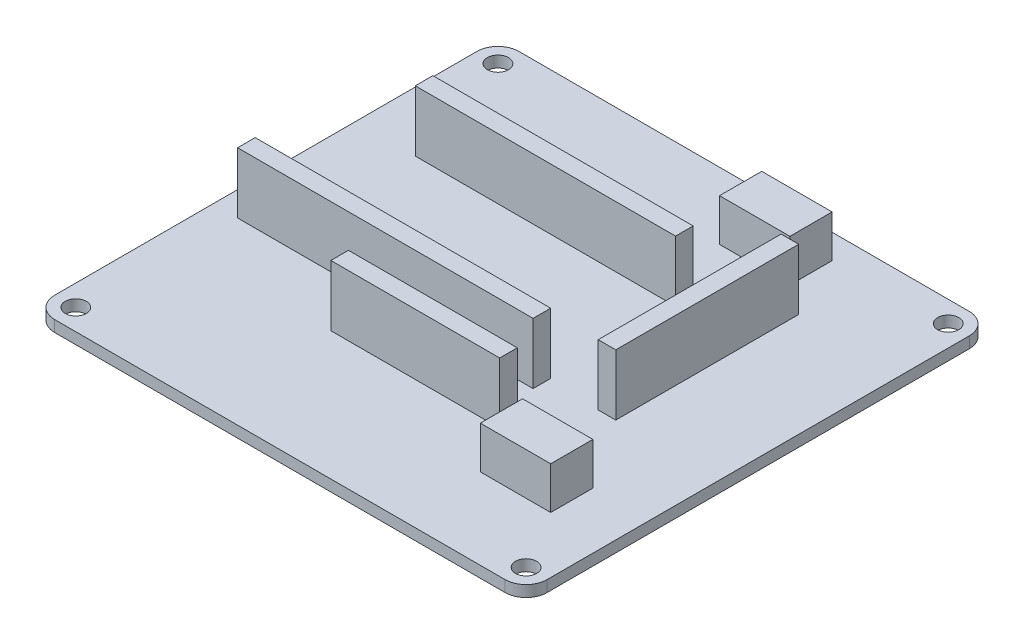
SolidWorks part; units mm, degrees
ref_plane "Front Plane" through (0, 0, 0) normal (0, 0, 1) x (1, 0, 0)
ref_plane "Top Plane" through (0, 0, 0) normal (0, 1, 0) x (1, 0, 0)
ref_plane "Right Plane" through (0, 0, 0) normal (1, 0, 0) x (0, 0, -1)
sketch "Sketch1" plane through (0, 0, 0) normal (0, 1, 0) x (1, 0, 0)
  line L0 (-32, 33) -> (32, 33)
  line L1 (35, -33) -> (-35, -33) construction
  line L2 (35, -33) -> (35, 33) construction
  line L3 (35, 33) -> (-35, 33) construction
  line L4 (-35, -33) -> (-35, 33) construction
  line L5 (35, -33) -> (-35, 33) construction
  line L6 (35, 33) -> (-35, -33) construction
  line L7 (-32, 30) -> (32, 30) construction
  line L8 (-32, 30) -> (-32, -30) construction
  line L9 (-32, -30) -> (32, -30) construction
  line L10 (32, 30) -> (32, -30) construction
  line L11 (35, 30) -> (35, -30)
  line L12 (32, -33) -> (-32, -33)
  line L13 (-35, -30) -> (-35, 30)
  circle A0 centre (-32, 30) radius 1.5
  circle A1 centre (32, 30) radius 1.5
  circle A2 centre (32, -30) radius 1.5
  circle A3 centre (-32, -30) radius 1.5
  arc A4 (-32, 33) -> (-35, 30) centre (-32, 30) ccw
  arc A5 (32, 33) -> (35, 30) centre (32, 30) cw
  arc A6 (35, -30) -> (32, -33) centre (32, -30) cw
  arc A7 (-35, -30) -> (-32, -33) centre (-32, -30) ccw
  point P0 (0, 0)
  point P8 (0, 0)
  point P14 (0, 30)
  point P16 (32, 0)
  point P25 (0, 0)
  dimension "D5" = 3
  dimension "D1" = 70
  dimension "D2" = 66
  dimension "D3" = 64
  dimension "D4" = 60
extrude "Boss-Extrude1" add sketch "Sketch1" along normal blind 1.6
sketch "Sketch2" plane through (0, 1.6, 0) normal (0, 1, 0) x (1, 0, 0)
  line L0 (32, 33) -> (-32, 33) construction
  line L25 (10.5, 12.75) -> (-26.5, 12.75)
  line L26 (10.5, 12.75) -> (10.5, 15.25)
  line L27 (10.5, 15.25) -> (-26.5, 15.25)
  line L28 (-26.5, 12.75) -> (-26.5, 15.25)
  line L29 (10.5, 12.75) -> (-26.5, 15.25) construction
  line L30 (10.5, 15.25) -> (-26.5, 12.75) construction
  line L31 (10.5, -7.5) -> (-31.5, -7.5)
  line L32 (10.5, -7.5) -> (10.5, -5)
  line L33 (10.5, -5) -> (-31.5, -5)
  line L34 (-31.5, -7.5) -> (-31.5, -5)
  line L35 (10.5, -7.5) -> (-31.5, -5) construction
  line L36 (10.5, -5) -> (-31.5, -7.5) construction
  line L37 (16, 29.5) -> (6, 29.5)
  line L38 (16, 29.5) -> (16, 23.5)
  line L39 (16, 23.5) -> (6, 23.5)
  line L40 (6, 29.5) -> (6, 23.5)
  line L41 (16, 29.5) -> (6, 23.5) construction
  line L42 (16, 23.5) -> (6, 29.5) construction
  line L43 (17.75, -5.5) -> (20.25, -5.5)
  line L44 (17.75, -5.5) -> (17.75, 20.5)
  line L45 (17.75, 20.5) -> (20.25, 20.5)
  line L46 (20.25, -5.5) -> (20.25, 20.5)
  line L47 (17.75, -5.5) -> (20.25, 20.5) construction
  line L48 (17.75, 20.5) -> (20.25, -5.5) construction
  line L49 (17, -15.5) -> (27, -15.5)
  line L50 (17, -15.5) -> (17, -21.5)
  line L51 (17, -21.5) -> (27, -21.5)
  line L52 (27, -15.5) -> (27, -21.5)
  line L53 (17, -15.5) -> (27, -21.5) construction
  line L54 (17, -21.5) -> (27, -15.5) construction
  line L55 (13, -14.75) -> (-11, -14.75)
  line L56 (13, -14.75) -> (13, -12.25)
  line L57 (13, -12.25) -> (-11, -12.25)
  line L58 (-11, -14.75) -> (-11, -12.25)
  line L59 (13, -14.75) -> (-11, -12.25) construction
  line L60 (13, -12.25) -> (-11, -14.75) construction
  line L61 (-35, 30) -> (-35, -30) construction
  line L62 (35, -30) -> (35, 30) construction
  line L63 (-32, -33) -> (32, -33) construction
  point P0 (-8, 14)
  point P5 (-10.5, -6.25)
  point P10 (11, 26.5)
  point P15 (19, 7.5)
  point P20 (22, -18.5)
  point P25 (1, -13.5)
  point P30 (17.6973, -17.7666)
  point P35 (-8.9596, -6.25)
  point P38 (19, 7.2625)
  point P41 (-5.5287, -13.5)
  dimension "D1" = 19
  dimension "D2" = 2.5
  dimension "D3" = 37
  dimension "D4" = 27
  dimension "D5" = 20.25
  dimension "D6" = 42
  dimension "D7" = 3.5
  dimension "D8" = 19
  dimension "D9" = 10
  dimension "D10" = 6
  dimension "D11" = 12.5
  dimension "D12" = 16
  dimension "D13" = 26
  dimension "D14" = 19.5
  dimension "D15" = 24
  dimension "D16" = 36
  dimension "D17" = 11.5
  dimension "D18" = 8
extrude "Boss-Extrude3" add sketch "Sketch2" along normal blind 6 contours L37 L40 L39 L38 | L52 L49 L50 L51 region at (11, 1.6, -26.5) region at (22, 1.6, 18.5)
extrude "Boss-Extrude4" add sketch "Sketch2<7>" along normal blind 8.65 contours L28 L25 L26 L27 | L43 L46 L45 L44 | L34 L31 L32 L33 | L58 L55 L56 L57 region at (-8, 1.6, -14) region at (-10.5, 1.6, 6.25) region at (19, 1.6, -7.5) region at (1, 1.6, 13.5)
sketch "Sketch2<7>" plane through (0, 1.6, 0) normal (0, 1, 0) x (1, 0, 0) same geometry as "Sketch2"
